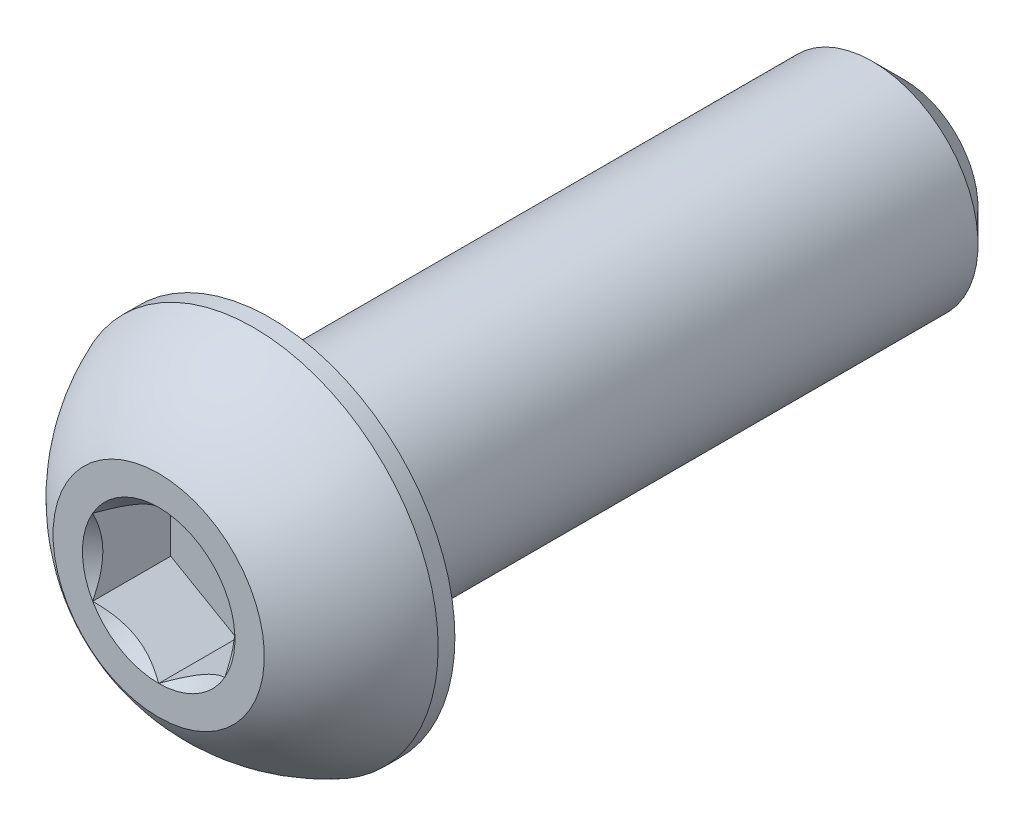
SolidWorks part; units mm, degrees
material "Alloy Steel"
ref_plane "Front" through (0, 0, 0) normal (0, 0, 1) x (1, 0, 0)
ref_plane "Top" through (0, 0, 0) normal (0, 1, 0) x (1, 0, 0)
ref_plane "Right" through (0, 0, 0) normal (1, 0, 0) x (0, 0, -1)
sketch "Sketch1" plane through (0, 0, 0) normal (1, 0, 0) x (0, 0, -1)
  line L2 (3.3528, 3.175) -> (22.4028, 3.175)
  line L3 (22.4028, 3.175) -> (22.4028, 0)
  line L4 (22.4028, 0) -> (3.3528, 0)
  line L6 (2.8499, 5.5499) -> (3.3528, 5.5499) construction
  line L7 (22.4028, 3.175) -> (22.4028, -3.175) construction
  line L8 (0, 0) -> (3.3528, 0) construction
  line L9 (3.3528, 5.5499) -> (3.3528, -5.5499) construction
  line L11 (3.3528, 3.175) -> (3.3528, 0)
  line L13 (0, 1.9844) -> (0, -1.9844) construction
  line L14 (0, 1.9844) -> (0, 3.175) construction
  arc A3 (0, 3.175) -> (2.8499, 5.5499) centre (5.0603, 0) cw construction
  dimension "D1" = 0.5029
revolve "Revolve1" add sketch "Sketch1" angle 360 mid plane about L4
sketch "Sketch3" plane through (0, 0, -22.4028) normal (0, 0, -1) x (-1, 0, 0)
  circle A0 centre (0, 0) radius 3.175
curve "Helix/Spiral1" pitch 1.27 height 20.32 turns 16
sketch "Sketch2" plane through (0, 0, 0) normal (1, 0, 0) x (0, 0, -1)
  line L0 (22.4028, 3.175) -> (23.514, 3.175)
  line L1 (23.514, 3.175) -> (23.0378, 2.3501)
  line L2 (23.0378, 2.3501) -> (22.879, 2.3501)
  line L3 (22.879, 2.3501) -> (22.4028, 3.175)
  line L4 (22.6409, 2.7626) -> (23.2759, 2.7626) construction
  dimension "D1" = 60
  dimension "D2" = 0.1588
  dimension "D3" = 0.635
chamfer "Chamfer1" distance 0.9525 angle 45 1 edges at (0, 3.175, -22.4028)
sweep "Cut-Sweep1" [suppressed] cut profiles "Sketch2" path "Helix/Spiral1"
sketch "Sketch7" plane through (0, 0, 0) normal (1, 0, 0) x (0, 0, -1)
  line L6 (2.8499, 5.5499) -> (3.3528, 5.5499) construction
  line L8 (0, 0) -> (3.3528, 0) construction
  line L11 (3.3528, 5.5499) -> (3.3528, -5.5499) construction
  line L12 (2.8499, 5.5499) -> (3.3528, 5.5499)
  line L13 (0, 0) -> (3.3528, 0)
  line L14 (0, 1.9844) -> (0, -1.9844) construction
  line L15 (3.3528, 5.5499) -> (3.3528, 0)
  line L16 (0, 3.175) -> (0, 0)
  arc A2 (2.8499, 5.5499) -> (0, 3.175) centre (5.0603, 0) ccw construction
  arc A3 (2.8499, 5.5499) -> (0, 3.175) centre (5.0603, 0) ccw
revolve "Revolve2" add sketch "Sketch7" angle 360 mid plane about L13
sketch "Sketch5" plane through (0, 0, 0) normal (0, 0, 1) x (1, 0, 0)
  line L1 (1.9844, -1.1457) -> (1.9844, 1.1457)
  line L2 (1.9844, 1.1457) -> (0, 2.2914)
  line L3 (0, 2.2914) -> (-1.9844, 1.1457)
  line L4 (-1.9844, 1.1457) -> (-1.9844, -1.1457)
  line L5 (-1.9844, -1.1457) -> (0, -2.2914)
  line L6 (0, -2.2914) -> (1.9844, -1.1457)
  circle A0 centre (0, 0) radius 1.9844 construction
extrude "Cut-Extrude2" cut sketch "Sketch5" against normal blind 2.347
sketch "Sketch6" plane through (0, 0, 0) normal (0, 0, 1) x (1, 0, 0)
  circle A0 centre (0, 0) radius 2.2914
extrude "Cut-Extrude3" cut sketch "Sketch6" against normal blind 2.347 draft 45
sketch "Sketch9" [suppressed] plane through (0, 0, -3.3528) normal (0, 0, 1) x (1, 0, 0)
  circle A2 centre (0, 0) radius 3.175
extrude "Boss-Extrude2" [suppressed] add sketch "Sketch9" against normal offset from surface (12.7 mm away) 22.225 up to face at (0, 2.2225, -22.4028)
sketch "Sketch10" plane through (0, 0, 0) normal (1, 0, 0) x (0, 0, -1)
  line L0 (22.4028, 3.175) -> (22.4028, -3.175) construction
  point P0 (20.4978, -3.175)
  dimension "D1" = 1.905
equation "\"D3@Helix/Spiral1\" = \"Lg@Sketch1\" + \"D4@Helix/Spiral1\""
equation "\"D2@Sketch2\" = \"D4@Helix/Spiral1\" * .125"
equation "\"D3@Sketch2\" = \"D4@Helix/Spiral1\" * .5"
equation "\"D1@Chamfer1\" = \"D4@Helix/Spiral1\" * .75"
equation "\"D1@Cut-Extrude2\" = \"Head Ht@Sketch1\" * .7"
equation "\"D1@Sketch1\" = \"Head Ht@Sketch1\" * .15"
equation "\"D1@Sketch10\" = \"D4@Helix/Spiral1\" * 1.5"
equation "\"D1@Cut-Extrude3\" = \"D1@Cut-Extrude2\""
